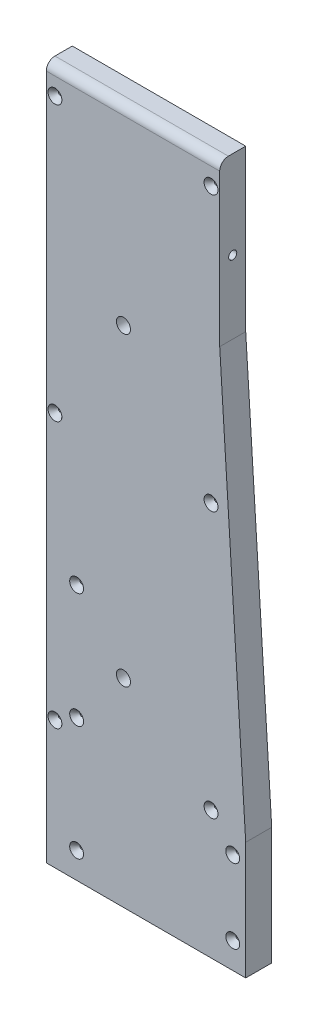
SolidWorks part; units mm, degrees
material "MDF"
ref_plane "Front Plane" through (0, 0, 0) normal (0, 0, 1) x (1, 0, 0)
ref_plane "Top Plane" through (0, 0, 0) normal (0, 1, 0) x (1, 0, 0)
ref_plane "Right Plane" through (0, 0, 0) normal (1, 0, 0) x (0, 0, -1)
sketch "Sketch1" plane through (0, 0, 0) normal (0, 0, 1) x (1, 0, 0)
  line L0 (82.0395, -5024.8784) -> (82.0395, -5533.4155)
  line L1 (82.0395, -5024.8784) -> (82.0395, -5464.9635) construction
  line L8 (-209.0395, -5024.8784) -> (-209.0395, -5142.5528)
  line L11 (-228.0888, -5533.4155) -> (228.0888, -5533.4155)
  line L14 (209.0395, -5142.5528) -> (209.0395, -5024.8784)
  line L15 (209.0395, -5024.8784) -> (-209.0395, -5024.8784)
  line L22 (209.0395, -5142.5528) -> (209.0395, -5024.8784)
  line L23 (209.0395, -5024.8784) -> (82.0395, -5024.8784)
  line L106 (82.0395, -5533.4155) -> (228.0888, -5533.4155)
  line L119 (-209.0395, -5142.5528) -> (-228.0888, -5447.3417)
  line L120 (-228.0888, -5447.3417) -> (-228.0888, -5533.4155)
  line L121 (228.0888, -5533.4155) -> (228.0888, -5447.3417)
  line L122 (228.0888, -5533.4155) -> (228.0888, -5447.3417)
  line L123 (228.0888, -5447.3417) -> (209.0395, -5142.5528)
  line L124 (228.0888, -5447.3417) -> (209.0395, -5142.5528)
  dimension "D1" = 0
extrude "Boss-Extrude1" add sketch "Sketch1" along normal blind 19.05
hole_wizard "3/8 Clearance Hole1" positions "Sketch2" profile "Sketch4" hole size "3/8" standard "ANSI Inch" end condition through all
sketch "Sketch2" plane through (0, 0, 19.05) normal (0, 0, 1) x (1, 0, 0)
  point P9 (138.551, -5387.9638)
  point P16 (138.551, -5164.3168)
  dimension "D1" = 223.647
sketch "Sketch4" plane through (138.551, -5387.9638, 19.05) normal (1, 0, 0) x (0, -1, 0)
  line L0 (0, 0) -> (0, 19.05)
  line L1 (0, 19.05) -> (5.1587, 19.05)
  line L2 (5.1587, 19.05) -> (5.1587, 0)
  line L5 (5.1587, 0) -> (0, 0)
  line L11 (0, -6.35) -> (0, 107.95) construction
  dimension "Thru Hole Dia." = 10.3175
  dimension "Thru Hole Depth" = 19.05
hole_wizard "Hole1" positions "Sketch5" profile "Sketch6" legacy
sketch "Sketch5" plane through (0, -5562.8703, 19.05) normal (0, 0, 1) x (1, 0, 0)
  line L0 (218.5638, 29.4548) -> (218.5638, 115.5175) construction
  line L4 (202.6895, 537.9919) -> (202.6895, 97.9067) construction
  line L9 (88.3895, 537.9919) -> (88.3895, 97.9067) construction
  line L13 (104.2638, 29.4548) -> (104.2638, 235.8996) construction
  line L16 (0, 537.9919) -> (0, 29.4548) construction
  point P0 (218.5638, 102.8175)
  point P2 (218.5638, 48.5048)
  point P33 (202.6895, 123.3067)
  point P35 (202.6895, 317.9493)
  point P37 (202.6895, 518.9419)
  point P51 (88.3895, 518.9419)
  point P53 (88.3895, 317.9493)
  point P55 (88.3895, 123.3067)
  point P69 (104.2638, 216.8496)
  point P71 (104.2638, 132.6772)
  point P73 (104.2638, 48.5048)
  point P83 (-104.2638, 48.5048)
  point P84 (-104.2638, 132.6772)
  point P85 (-104.2638, 216.8496)
  point P86 (-88.3895, 123.3067)
  point P87 (-88.3895, 317.9493)
  point P88 (-88.3895, 518.9419)
  point P89 (-202.6895, 518.9419)
  point P90 (-202.6895, 317.9493)
  point P91 (-202.6895, 123.3067)
  point P92 (-218.5638, 48.5048)
  point P93 (-218.5638, 102.8175)
sketch "Sketch6" plane through (218.5638, -5460.0528, 19.05) normal (1, 0, 0) x (0, -1, 0)
  line L0 (0, 0) -> (0, 51.7539)
  line L1 (0, 51.7539) -> (1.5875, 50.8)
  line L2 (1.5875, 50.8) -> (1.5875, 4.0177)
  line L3 (1.5875, 4.0177) -> (5.08, 0)
  line L4 (5.08, 0) -> (0, 0)
  line L5 (0, -14.3089) -> (0, 102.4216) construction
  line L6 (0, 51.7539) -> (-1.5875, 50.8) construction
  line L7 (-1.5875, 4.0177) -> (-5.08, 0) construction
  dimension "Diameter" = 3.175
  dimension "Depth" = 50.8
  dimension "C-Sink Diameter" = 10.16
  dimension "C-Sink Angle" = 82
  dimension "Drill Angle" = 118
hole_wizard "15/64 (0.23438) Diameter Hole1" positions "Sketch7" profile "Sketch9" hole size "15/64" standard "ANSI Inch"
sketch "Sketch7" plane through (209.0395, 0, 0) normal (1, 0, 0) x (0, 0, -1)
  point P0 (-9.5266, -5089.2261)
sketch "Sketch9" plane through (209.0395, -5089.2261, 9.5266) normal (0, 1, 0) x (0, 0, -1)
  line L0 (0, 0) -> (0, 25.4)
  line L1 (0, 25.4) -> (2.9766, 23.6115)
  line L2 (2.9766, 23.6115) -> (2.9766, 0)
  line L5 (2.9766, 0) -> (0, 0)
  line L10 (0, 25.4) -> (-2.9766, 23.6115) construction
  line L11 (0, -6.35) -> (0, 107.95) construction
  dimension "Hole Dia." = 5.9533
  dimension "Hole Depth" = 25.4
  dimension "Drill Angle" = 118
fillet "Fillet1" radius 6.35 1 edges at (145.5395, -5024.8784, 19.05)
